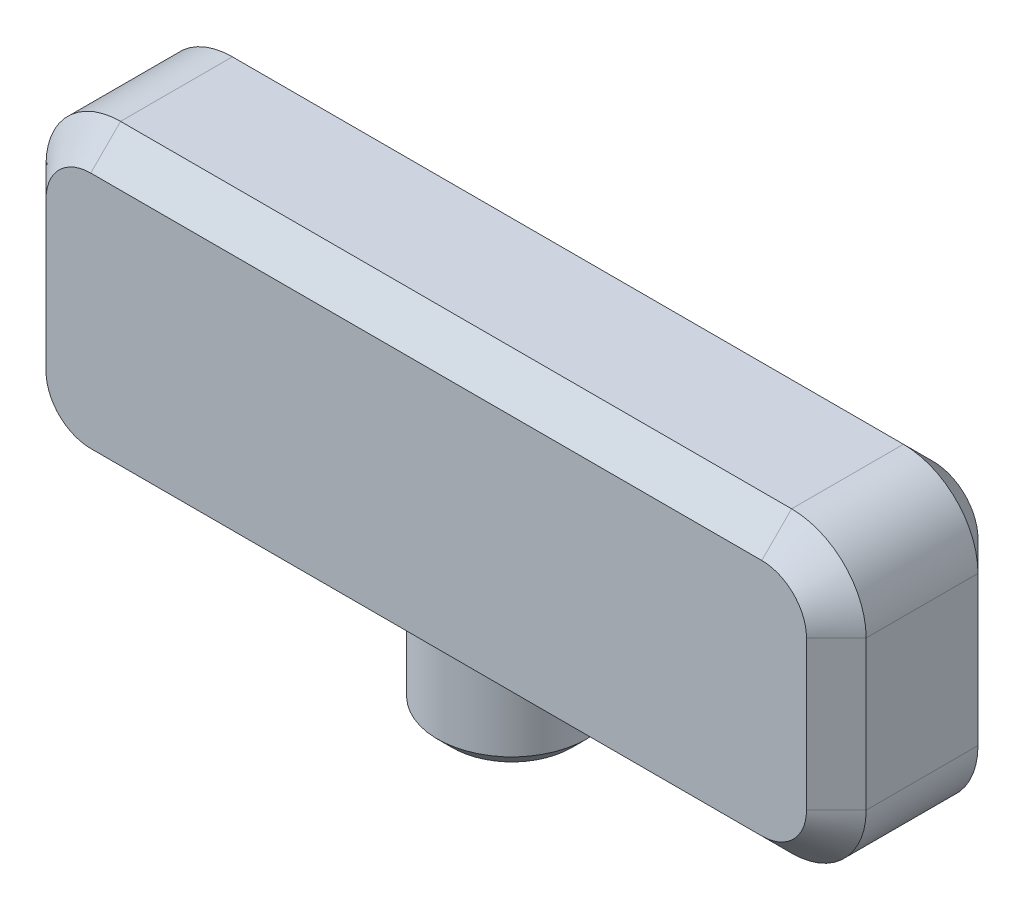
SolidWorks part; units mm, degrees
material "PE High Density"
ref_plane "Front Plane" through (0, 0, 0) normal (0, 0, 1) x (1, 0, 0)
ref_plane "Top Plane" through (0, 0, 0) normal (0, 1, 0) x (1, 0, 0)
ref_plane "Right Plane" through (0, 0, 0) normal (1, 0, 0) x (0, 0, -1)
sketch "Sketch1" plane through (0, 0, 0) normal (0, 0, 1) x (1, 0, 0)
  line L0 (44.45, 0) -> (-44.45, 0)
  line L1 (69.85, -25.4) -> (-69.85, -25.4)
  line L2 (69.85, -25.4) -> (69.85, 25.4)
  line L3 (69.85, 25.4) -> (-69.85, 25.4)
  line L4 (-69.85, -25.4) -> (-69.85, 25.4)
  line L5 (69.85, -25.4) -> (-69.85, 25.4) construction
  line L6 (69.85, 25.4) -> (-69.85, -25.4) construction
  circle A0 centre (44.45, 0) radius 5.715
  circle A1 centre (-44.45, 0) radius 5.715
  point P0 (0, 0)
  point P13 (0, 0)
  dimension "D1" = 11.43
  dimension "D2" = 50.8
  dimension "2" = 44.45
  dimension "4.5" = 139.7
extrude "Boss-Extrude1" add sketch "Sketch1" along normal blind 22.86 contours L4 L1 L2 L3 A1 A0 region at (0, -23.9135, 0)
extrude "Boss-Extrude2" add sketch "Sketch1<3>" along normal blind 6.35 from surface contours L4 L1 L2 L3 A1 A0 | A1 | A0 region at (-50.0034, 0, 0) region at (44.45, 5.5534, 0) region at (0, -23.9135, 0) starting at face at (-38.735, 0, 22.86)
sketch "Sketch1<3>" plane through (0, 0, 0) normal (0, 0, 1) x (1, 0, 0) same geometry as "Sketch1"
extrude "Extrude-Thin1" add sketch "Sketch1<4>" against normal blind 7.62 thin contours A0 | A1 thin type one direction wall 7.62
sketch "Sketch1<4>" plane through (0, 0, 0) normal (0, 0, 1) x (1, 0, 0) same geometry as "Sketch1"
fillet "Fillet1" radius 12.7 4 edges at (-69.85, -25.4, 14.605) (69.85, -25.4, 14.605) (69.85, 25.4, 14.605) (-69.85, 25.4, 14.605)
chamfer "Chamfer1" distance 5.08 angle 45 16 edges at (66.1303, -21.6803, 0) (69.85, 0, 0) (66.1303, 21.6803, 0) (0, 25.4, 0) (-66.1303, 21.6803, 0) (-69.85, 0, 0) (-66.1303, -21.6803, 0) (0, -25.4, 0) (-66.1303, 21.6803, 29.21) (0, 25.4, 29.21) (66.1303, 21.6803, 29.21) (69.85, 0, 29.21) (66.1303, -21.6803, 29.21) (0, -25.4, 29.21) (-66.1303, -21.6803, 29.21) (-69.85, 0, 29.21)
chamfer "Chamfer3" distance 2.54 angle 45 4 edges at (-38.735, 0, -7.62) (50.165, 0, -7.62) (57.785, 0, -7.62) (-31.115, 0, -7.62)
sketch "Sketch2" plane through (0, -25.4, 0) normal (0, -1, 0) x (1, 0, 0)
  line L0 (-57.15, 24.13) -> (-57.15, 5.08) construction
  circle A0 centre (0, 14.605) radius 12.7
  circle A1 centre (0, 14.605) radius 5.08
  point P4 (-57.15, 14.605)
  dimension "D1" = 25.4
  dimension "D2" = 10.16
extrude "Boss-Extrude3" add sketch "Sketch2" along normal blind 12.7 and the other way blind 12.7
extrude "Cut-Extrude1" cut sketch "Sketch2<2>" against normal blind 26.67 contours A1 region at (0, -25.4, 14.605)
sketch "Sketch2<2>" plane through (0, -25.4, 0) normal (0, -1, 0) x (1, 0, 0) same geometry as "Sketch2"
chamfer "Chamfer2" distance 2.54 angle 45 1 edges at (12.7, -38.1, 14.605)
